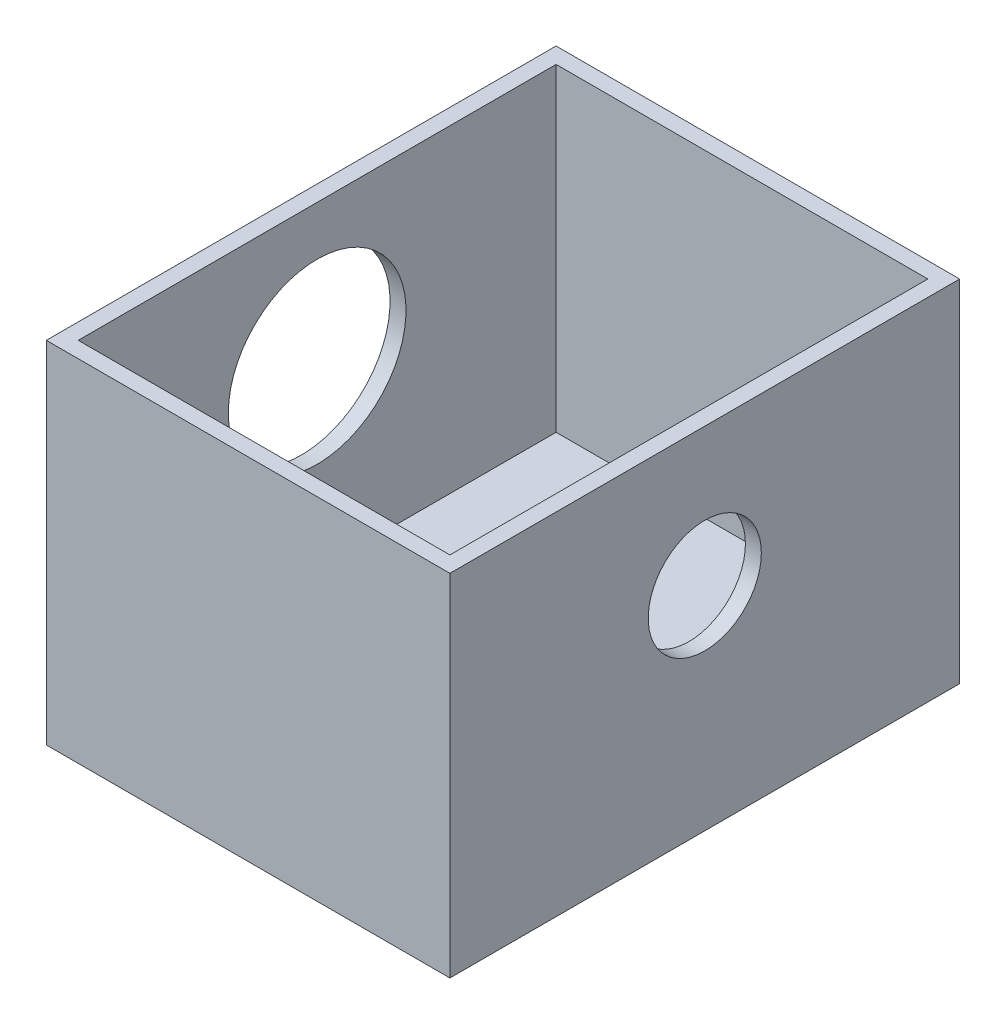
SolidWorks part; units mm, degrees
ref_plane "Front Plane" through (0, 0, 0) normal (0, 0, 1) x (1, 0, 0)
ref_plane "Top Plane" through (0, 0, 0) normal (0, 1, 0) x (1, 0, 0)
ref_plane "Right Plane" through (0, 0, 0) normal (1, 0, 0) x (0, 0, -1)
sketch "Sketch1" plane through (0, 0, 0) normal (0, 1, 0) x (1, 0, 0)
  line L0 (-7.9678, 7.5757) -> (-7.9678, -4.6163)
  line L1 (-7.9678, -4.6163) -> (1.6842, -4.6163)
  line L2 (1.6842, -4.6163) -> (1.6842, 7.5757)
  line L3 (1.6842, 7.5757) -> (-7.9678, 7.5757)
  dimension "D1" = 12.192
  dimension "D2" = 9.652
extrude "Boss-Extrude1" add sketch "Sketch1" along normal blind 8.382
sketch "Sketch4" plane through (0, 8.382, 0) normal (0, 1, 0) x (1, 0, 0)
  line L0 (1.3032, -4.2353) -> (1.3032, 7.1947)
  line L1 (1.3032, 7.1947) -> (-7.5868, 7.1947)
  line L2 (-7.5868, 7.1947) -> (-7.5868, -4.2353)
  line L3 (-7.5868, -4.2353) -> (1.3032, -4.2353)
  line L5 (-7.9678, 7.5757) -> (-7.9678, -4.6163) construction
  line L7 (1.6842, 7.5757) -> (-7.9678, 7.5757) construction
  dimension "D1" = 8.89
  dimension "D2" = 0.381
  dimension "D3" = 11.43
  dimension "D4" = 0.381
extrude "Cut-Extrude1" cut sketch "Sketch4" against normal blind 7.62
sketch "Sketch6" plane through (-7.9678, 0, 0) normal (-1, 0, 0) x (0, 0, 1)
  line L0 (-7.5757, 8.382) -> (-7.5757, 0) construction
  line L1 (-7.5757, 0) -> (4.6163, 0) construction
  circle A0 centre (-1.4797, 5.08) radius 2.1247
  dimension "D2" = 4.2494
  dimension "D1" = 5.08
  dimension "D3" = 6.096
extrude "Cut-Extrude2" cut sketch "Sketch6" against normal up to next
ref_plane "Plane1" through (0, 0, -1.4797) normal (0, 0, 1) x (1, 0, 0)
ref_plane "Plane2" through (-3.1418, 0, 0) normal (1, 0, 0) x (0, 0, -1)
ref_axis "Axis1" through (-7.5868, 5.08, -1.4797) along (-1, 0, 0)
hole_wizard "#6-32 Tapped Hole2" positions "Sketch11" profile "Sketch12" tap size "#6-32" standard "ANSI Inch" end condition up to next
sketch "Sketch11" plane through (1.6842, 0, 0) normal (1, 0, 0) x (0, 0, -1)
  point P0 (1.4797, 5.08)
sketch "Sketch12" plane through (1.6842, 5.08, -1.4797) normal (0, 1, 0) x (0, 0, -1)
  line L0 (0, 0) -> (0, 0.381)
  line L1 (0, 0.381) -> (1.3525, 0.381)
  line L2 (1.3525, 0.381) -> (1.3525, 0)
  line L5 (1.3525, 0) -> (0, 0)
  line L11 (0, -6.35) -> (0, 107.95) construction
  dimension "Thread Major Dia." = 2.7051
  dimension "Thru Tap Drill Depth" = 0.381
